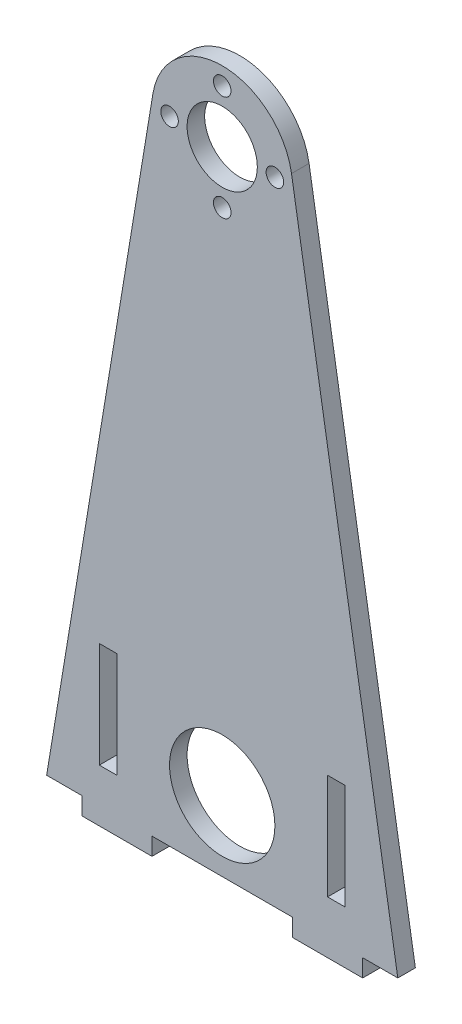
SolidWorks part; units mm, degrees
material "Pine"
ref_plane "Front Plane" through (0, 0, 0) normal (0, 0, 1) x (1, 0, 0)
ref_plane "Top Plane" through (0, 0, 0) normal (0, 1, 0) x (1, 0, 0)
ref_plane "Right Plane" through (0, 0, 0) normal (1, 0, 0) x (0, 0, -1)
sketch "Sketch1" plane through (0, 0, 0) normal (0, 0, 1) x (1, 0, 0)
  line L0 (0, 0) -> (0, 228.6) construction
  line L1 (25.4, 0) -> (-25.4, 0)
  line L2 (-25.4, 0) -> (-25.4, -6.35)
  line L3 (-25.4, -6.35) -> (-50.8, -6.35)
  line L4 (-50.8, -6.35) -> (-50.8, 0)
  line L5 (-50.8, 0) -> (-63.5, 0)
  line L6 (-63.5, 0) -> (-25.0605, 232.739)
  line L7 (0, 228.6) -> (0, 159.1888) construction
  line L8 (50.8, 0) -> (63.5, 0)
  line L9 (50.8, -6.35) -> (50.8, 0)
  line L10 (25.4, 0) -> (25.4, -6.35)
  line L11 (25.4, -6.35) -> (50.8, -6.35)
  line L12 (63.5, 0) -> (25.0605, 232.739)
  line L13 (44.45, 12.7) -> (38.1, 12.7)
  line L14 (-44.45, 12.7) -> (-38.1, 12.7)
  line L15 (-44.45, 12.7) -> (-44.45, 50.8)
  line L16 (-44.45, 50.8) -> (-38.1, 50.8)
  line L17 (-38.1, 12.7) -> (-38.1, 50.8)
  line L22 (44.45, 12.7) -> (44.45, 50.8)
  line L23 (44.45, 50.8) -> (38.1, 50.8)
  line L24 (38.1, 12.7) -> (38.1, 50.8)
  line L27 (-38.1, 0) -> (-38.1, 12.7) construction
  line L28 (-44.45, 12.7) -> (-44.45, 0) construction
  arc A0 (25.0605, 232.739) -> (-25.0605, 232.739) centre (0, 228.6) ccw
  circle A1 centre (0, 228.6) radius 12.7
  circle A3 centre (0, 247.65) radius 3.175
  circle A4 centre (19.05, 228.6) radius 3.175
  circle A5 centre (0, 209.55) radius 3.175
  circle A6 centre (-19.05, 228.6) radius 3.175
  circle A7 centre (0, 25.4) radius 19.05
  point P31 (0, 0)
  point P42 (0, 228.6)
  dimension "D5" = 12.7
  dimension "D7" = 25.4
  dimension "D8" = 38.1
  dimension "D13" = 6.35
  dimension "D1" = 63.5
  dimension "D2" = 6.35
  dimension "D3" = 25.4
  dimension "D4" = 25.4
  dimension "D6" = 228.6
  dimension "D9" = 25.4
  dimension "D10" = 38.1
  dimension "D11" = 12.7
  dimension "D12" = 19.05
  dimension "D14" = 4
extrude "Boss-Extrude1" add sketch "Sketch1" along normal blind 6.35
